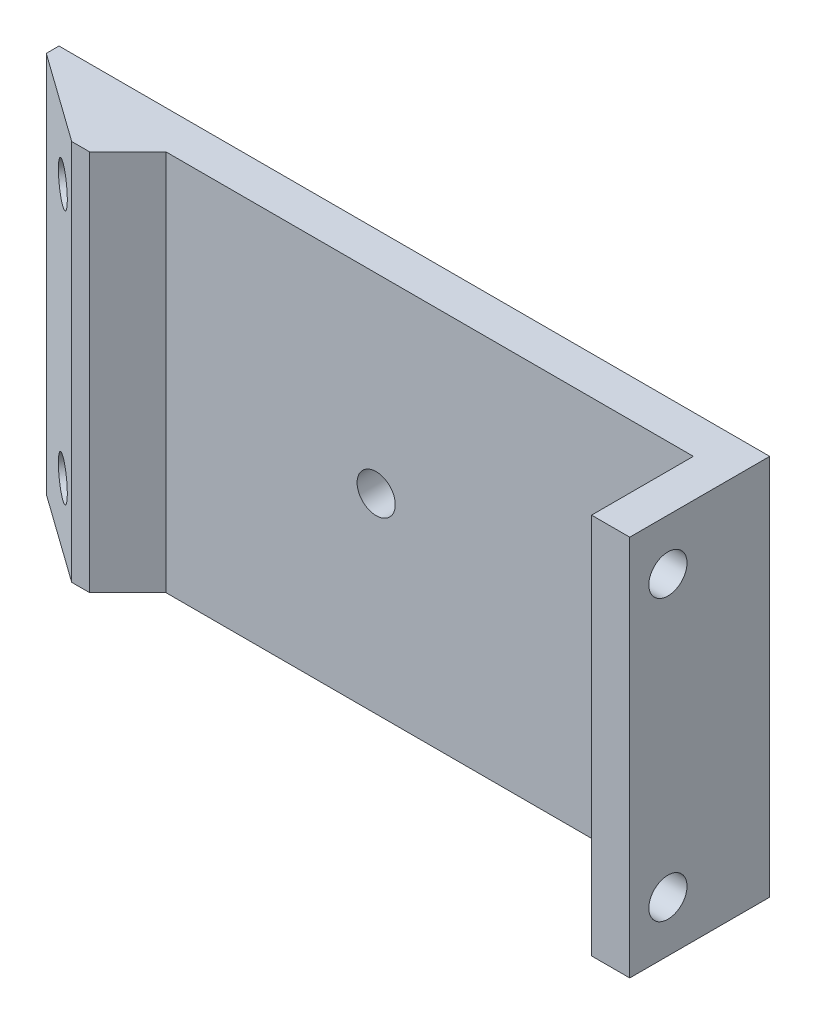
SolidWorks part; units mm, degrees
ref_plane "Front Plane" through (0, 0, 0) normal (0, 0, 1) x (1, 0, 0)
ref_plane "Top Plane" through (0, 0, 0) normal (0, 1, 0) x (1, 0, 0)
ref_plane "Right Plane" through (0, 0, 0) normal (1, 0, 0) x (0, 0, -1)
sketch "Sketch1" plane through (0, 0, 0) normal (0, 0, 1) x (1, 0, 0)
  line L1 (-27.925, -15) -> (27.925, -15)
  line L2 (-27.925, -15) -> (-27.925, 15)
  line L3 (-27.925, 15) -> (27.925, 15)
  line L4 (27.925, -15) -> (27.925, 15)
  line L5 (-27.925, -15) -> (27.925, 15) construction
  line L6 (-27.925, 15) -> (27.925, -15) construction
  point P0 (0, 0)
  dimension "D1" = 55.85
  dimension "D2" = 30
extrude "Boss-Extrude1" add sketch "Sketch1" along normal blind 3
sketch "Sketch2" plane through (0, 0, 3) normal (0, 0, 1) x (1, 0, 0)
  line L0 (-27.925, -15) -> (27.925, -15) construction
  line L1 (-27.925, 15) -> (-19.525, 15)
  line L2 (-27.925, 15) -> (-27.925, -15)
  line L3 (-27.925, -15) -> (-19.525, -15)
  line L4 (-19.525, 15) -> (-19.525, -15)
  dimension "D1" = 8.4
extrude "Boss-Extrude2" add sketch "Sketch2" along normal blind 3
chamfer "Chamfer1" distance 5 distance2 7 1 edges at (-27.925, 0, 6) first distance on face at (-27.925, 0, 3)
sketch "Sketch3" plane through (-9.9071, 0, 13.8699) normal (-0.5812, 0, 0.8137) x (0.8137, 0, 0.5812)
  line L0 (-22.1423, 15) -> (-13.5399, 15) construction
  line L1 (-13.5399, -15) -> (-22.1423, -15) construction
  line L2 (-13.5399, 15) -> (-13.5399, -15) construction
  circle A0 centre (-16.5399, 10) radius 1.5
  circle A1 centre (-16.5399, -10) radius 1.5
  dimension "D1" = 3
  dimension "D2" = 3
  dimension "D3" = 5
  dimension "D4" = 5
  dimension "D6" = 3
  dimension "D5" = 3
extrude "Cut-Extrude1" cut sketch "Sketch3" against normal blind 3
chamfer "Chamfer2" distance 3 angle 45 1 edges at (-19.525, 0, 3)
sketch "Sketch4" plane through (-9.9071, 0, 13.8699) normal (-0.5812, 0, 0.8137) x (0.8137, 0, 0.5812)
  line L1 (-14.7305, 7.3906) -> (-13.3754, 10.2623)
  line L2 (-13.3754, 10.2623) -> (-15.1848, 12.8718)
  line L3 (-15.1848, 12.8718) -> (-18.3494, 12.6094)
  line L4 (-18.3494, 12.6094) -> (-19.7045, 9.7377)
  line L5 (-19.7045, 9.7377) -> (-17.8951, 7.1282)
  line L6 (-17.8951, 7.1282) -> (-14.7305, 7.3906)
  line L7 (-14.7305, -7.3906) -> (-17.8951, -7.1282)
  line L8 (-17.8951, -7.1282) -> (-19.7045, -9.7377)
  line L9 (-19.7045, -9.7377) -> (-18.3494, -12.6094)
  line L10 (-18.3494, -12.6094) -> (-15.1848, -12.8718)
  line L11 (-15.1848, -12.8718) -> (-13.3754, -10.2623)
  line L12 (-13.3754, -10.2623) -> (-14.7305, -7.3906)
  circle A0 centre (-16.5399, 10) radius 2.75 construction
  circle A1 centre (-16.5399, -10) radius 2.75 construction
  dimension "D1" = 5.5
  dimension "D2" = 5.5
extrude "Cut-Extrude2" cut sketch "Sketch4" against normal blind 8 from offset 3 offset against normal yes
sketch "Sketch5" plane through (0, 0, 3) normal (0, 0, 1) x (1, 0, 0)
  line L0 (-16.525, -15) -> (27.925, -15) construction
  line L1 (27.925, 15) -> (24.925, 15)
  line L2 (27.925, 15) -> (27.925, -15)
  line L3 (27.925, -15) -> (24.925, -15)
  line L4 (24.925, 15) -> (24.925, -15)
  dimension "D1" = 3
extrude "Boss-Extrude3" add sketch "Sketch5" along normal blind 8
sketch "Sketch6" plane through (27.925, 0, 0) normal (1, 0, 0) x (0, 0, -1)
  line L0 (-11, -15) -> (-11, 15) construction
  line L1 (-11, 15) -> (0, 15) construction
  line L2 (-11, -15) -> (0, -15) construction
  circle A0 centre (-8, 11) radius 1.5
  circle A1 centre (-8, -11) radius 1.5
  dimension "D1" = 3
  dimension "D2" = 3
  dimension "D3" = 3
  dimension "D4" = 3
  dimension "D5" = 4
  dimension "D6" = 4
extrude "Cut-Extrude3" cut sketch "Sketch6" against normal blind 8
sketch "Sketch7" plane through (0, 0, 0) normal (0, 0, -1) x (-1, 0, 0)
  circle A0 centre (0, 0) radius 1.5
  dimension "D1" = 3
  dimension "D2" = 0
extrude "Cut-Extrude4" cut sketch "Sketch7" against normal through all
